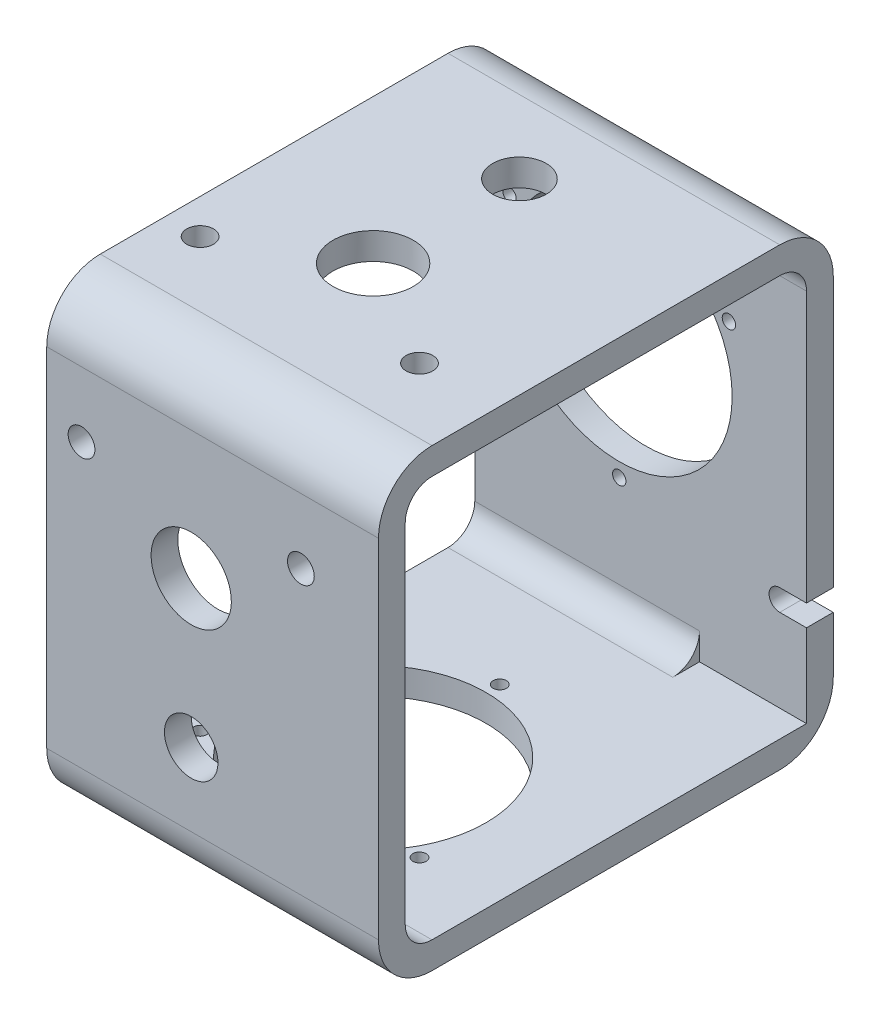
SolidWorks part; units mm, degrees
material "ABS"
ref_plane "前视基准面" through (0, 0, 0) normal (0, 0, 1) x (1, 0, 0)
ref_plane "上视基准面" through (0, 0, 0) normal (0, 1, 0) x (1, 0, 0)
ref_plane "右视基准面" through (0, 0, 0) normal (1, 0, 0) x (0, 0, -1)
sketch "草图2" plane through (0, 0, 0) normal (1, 0, 0) x (0, 0, -1)
  line L0 (-42.5, -42.5) -> (42.5, -42.5)
  line L1 (-37.5, -37.5) -> (37.5, -37.5)
  line L2 (-37.5, -37.5) -> (-37.5, 37.5)
  line L3 (-37.5, 37.5) -> (37.5, 37.5)
  line L4 (37.5, -37.5) -> (37.5, 37.5)
  line L5 (-37.5, -37.5) -> (37.5, 37.5) construction
  line L6 (-37.5, 37.5) -> (37.5, -37.5) construction
  line L7 (42.5, -42.5) -> (42.5, 42.5)
  line L8 (-42.5, 42.5) -> (42.5, 42.5)
  line L9 (-42.5, -42.5) -> (-42.5, 42.5)
  point P0 (0, 0)
  dimension "D1" = 75
  dimension "D2" = 75
  dimension "D3" = 5
extrude "凸台-拉伸1" add sketch "草图2" along normal blind 70
sketch "草图3" plane through (0, 0, -37.5) normal (0, 0, 1) x (1, 0, 0)
  line L0 (70, 37.5) -> (0, 37.5) construction
  circle A0 centre (35, 8.5) radius 21.1
  dimension "D1" = 42.2
  dimension "D2" = 29
extrude "切除-拉伸1" cut sketch "草图3" against normal blind 10
sketch "草图4" plane through (0, 0, -37.5) normal (0, 0, 1) x (1, 0, 0)
  line L0 (70, -37.5) -> (70, 37.5) construction
  line L1 (14.5, 20.3357) -> (35, -15.1714) construction
  line L2 (35, -15.1714) -> (55.5, 20.3357) construction
  line L3 (55.5, 20.3357) -> (14.5, 20.3357) construction
  circle A0 centre (35, 8.5) radius 11.8357 construction
  circle A1 centre (14.5, 20.3357) radius 1.25
  circle A2 centre (35, -15.1714) radius 1.25
  circle A3 centre (55.5, 20.3357) radius 1.25
  dimension "D3" = 2.5
  dimension "D1" = 41
  dimension "D2" = 90
extrude "切除-拉伸2" cut sketch "草图4" against normal blind 10
ref_axis "基准轴1" through (0, 0, 0) along (1, 0, 0)
ref_plane "基准面1" through (0, 0, 0) normal (0, 0.7071, -0.7071) x (-1, 0, 0)
mirror "镜向1" about plane through (0, 0, 0) normal (0, 0.7071, -0.7071) of "切除-拉伸1", "切除-拉伸2"
fillet "圆角1" radius 5 4 edges at (35, 37.5, 37.5) (35, -37.5, 37.5) (35, -37.5, -37.5) (35, 37.5, -37.5)
fillet "圆角2" radius 10 4 edges at (35, 42.5, 42.5) (35, -42.5, 42.5) (35, -42.5, -42.5) (35, 42.5, -42.5)
sketch "草图5" plane through (0, 0, 0) normal (-1, 0, 0) x (0, 0, 1)
  line L1 (-48.7074, 62.8892) -> (48.7074, 62.8892)
  line L2 (-48.7074, 62.8892) -> (-48.7074, -62.8892)
  line L3 (-48.7074, -62.8892) -> (48.7074, -62.8892)
  line L4 (48.7074, 62.8892) -> (48.7074, -62.8892)
  line L5 (-48.7074, 62.8892) -> (48.7074, -62.8892) construction
  line L6 (-48.7074, -62.8892) -> (48.7074, 62.8892) construction
  point P0 (0, 0)
extrude "切除-拉伸3" cut sketch "草图5" against normal blind 8
sketch "草图6" plane through (0, 42.5, 0) normal (0, 1, 0) x (1, 0, 0)
  line L1 (70, 37.5) -> (8, 37.5) construction
  line L2 (8, -32.5) -> (8, 32.5) construction
  circle A0 centre (35, 18.85) radius 5
  dimension "D1" = 10
  dimension "D2" = 18.65
  dimension "D3" = 27
extrude "切除-拉伸4" cut sketch "草图6" against normal blind 10
mirror "镜向2" about plane through (0, 0, 0) normal (0, 0.7071, -0.7071) of "切除-拉伸4"
sketch "草图13" plane through (0, 42.5, 0) normal (0, 1, 0) x (1, 0, 0)
  circle A0 centre (35, -8.5) radius 7.5
  circle A1 centre (55.5, -20.3357) radius 2.5
  circle A3 centre (14.5, -20.3357) radius 2.5
  dimension "D1" = 5
  dimension "D2" = 5
  dimension "D3" = 15
extrude "切除-拉伸7" cut sketch "草图13" against normal blind 31
mirror "镜向5" about plane through (0, 0, 0) normal (0, 0.7071, -0.7071) of "切除-拉伸7"
sketch "草图15" plane through (0, 0, -37.5) normal (0, 0, 1) x (1, 0, 0)
  line L0 (70, -32.5) -> (70, 32.5) construction
  line L1 (50, -21.5) -> (70, -21.5)
  line L2 (50, -21.5) -> (50, -37.5)
  line L3 (50, -37.5) -> (70, -37.5)
  line L4 (70, -21.5) -> (70, -37.5)
  line L5 (70, -37.5) -> (8, -37.5) construction
  dimension "D1" = 16
  dimension "D2" = 20
  dimension "D3" = 0
  dimension "D4" = 0
extrude "切除-拉伸8" cut sketch "草图15" along normal blind 12
sketch "草图16" plane through (0, 0, -37.5) normal (0, 0, 1) x (1, 0, 0)
  line L0 (65, -19.9908) -> (70, -19.9908) construction
  line L1 (70, -37.5) -> (70, 32.5) construction
  line L2 (65, -17.9908) -> (70, -17.9908)
  line L3 (65, -21.9908) -> (70, -21.9908)
  arc A0 (65, -17.9908) -> (65, -21.9908) centre (65, -19.9908) ccw
  arc A1 (70, -21.9908) -> (70, -17.9908) centre (70, -19.9908) ccw
  point P4 (67.5, -19.9908)
  dimension "D1" = 2
  dimension "D2" = 5
extrude "切除-拉伸9" cut sketch "草图16" against normal blind 12
